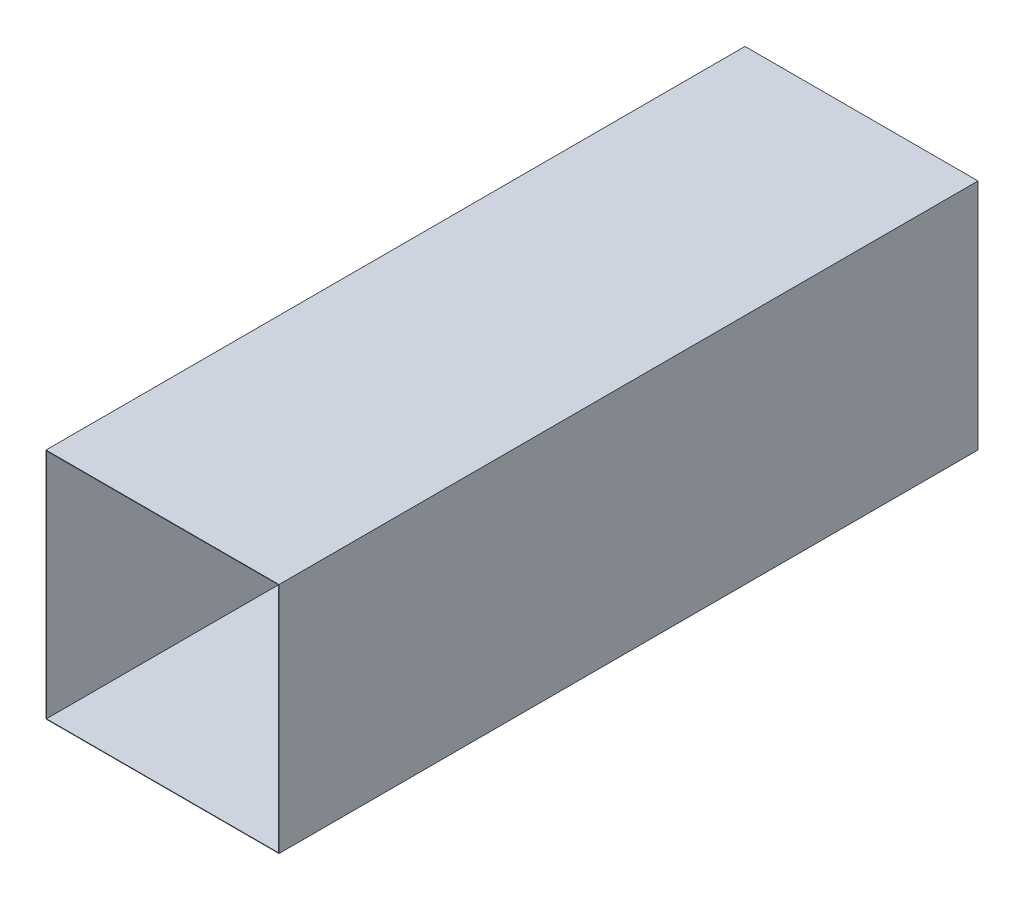
SolidWorks part; units mm, degrees
material "Plain Carbon Steel"
ref_plane "Front Plane" through (0, 0, 0) normal (0, 0, 1) x (1, 0, 0)
ref_plane "Top Plane" through (0, 0, 0) normal (0, 1, 0) x (1, 0, 0)
ref_plane "Right Plane" through (0, 0, 0) normal (1, 0, 0) x (0, 0, -1)
sketch "DuctSketch" plane through (0, 0, 0) normal (0, 0, 1) x (1, 0, 0)
  line L1 (-500, 500) -> (500, 500)
  line L2 (-500, 500) -> (-500, -500)
  line L3 (-500, -500) -> (500, -500)
  line L4 (500, 500) -> (500, -500)
  line L5 (-500, 500) -> (500, -500) construction
  line L6 (-500, -500) -> (500, 500) construction
  point P0 (0, 0)
  dimension "Height" = 1000
  dimension "Width" = 1000
extrude "Extrusion" add sketch "DuctSketch" along normal blind 3000 thin thin type one direction reverse wall 2
sketch "FilterSketch" plane through (0, 0, 0) normal (0, 0, -1) x (-1, 0, 0)
  line L1 (-500, -500) -> (500, -500)
  line L2 (-500, -500) -> (-500, 500)
  line L3 (-500, 500) -> (500, 500)
  line L4 (500, -500) -> (500, 500)
  dimension "NominalHeight" = 1000
  dimension "NominalWidth" = 1000
